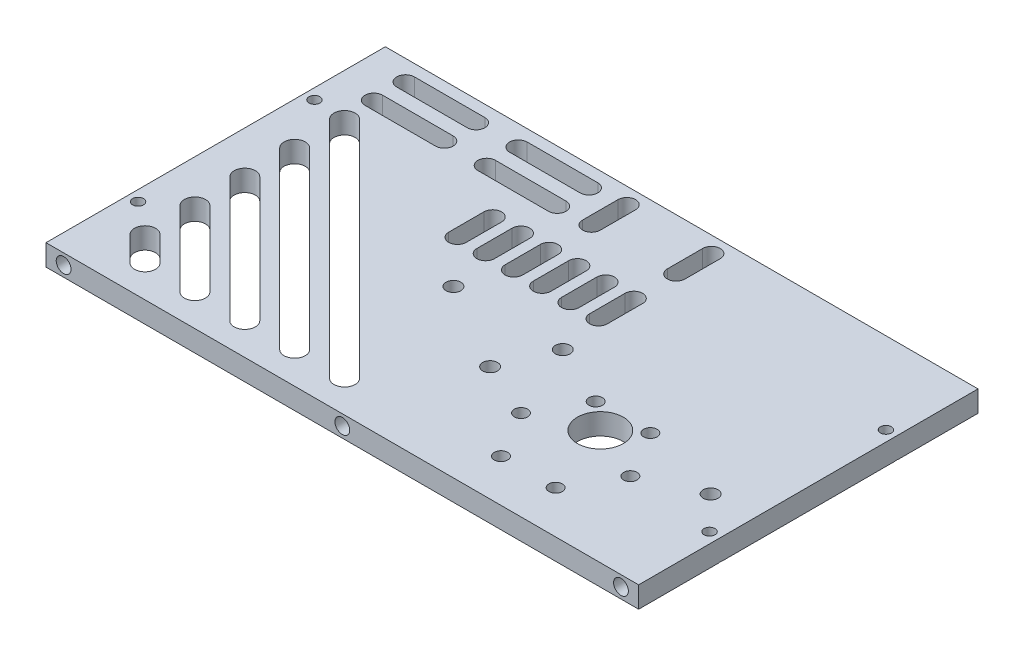
SolidWorks part; units mm, degrees
ref_plane "Front Plane" through (0, 0, 0) normal (1, 0, 0) x (0, 1, 0)
ref_plane "Top Plane" through (0, 0, 0) normal (0, 0, 1) x (0, 1, 0)
ref_plane "Right Plane" through (0, 0, 0) normal (0, 1, 0) x (-1, 0, 0)
sketch "Sketch1" plane through (0, 0, 0) normal (0, 1, 0) x (-1, 0, 0)
  line L3 (168, 0) -> (0, 0)
  line L10 (0, 96.2019) -> (168, 96.2019)
  line L15 (168, 96.2019) -> (168, 0)
  line L17 (0, 96.2019) -> (0, 0)
  point P16 (-5.5507, 58)
  point P19 (0, 0)
  point P27 (168, 0)
  dimension "D1" = 168
  dimension "D3" = 96.2019
extrude "Boss-Extrude1" add sketch "Sketch1" along normal blind 6 contours L10 L17 L3 L15 region at (-84, 0, 48.1009)
sketch "Sketch2" plane through (0, 0, 0) normal (0, -1, 0) x (1, 0, 0)
  line L0 (-93.9294, 6) -> (46.9505, 6) construction
  line L1 (-153.4835, 90.2019) -> (20.1803, 90.2019) construction
  line L2 (-28.5825, 49.2019) -> (48.7007, 49.2019) construction
  line L3 (-61.85, 63.025) -> (-61.85, 73.1366) construction
  line L4 (-168, 96.2019) -> (-168, 0) construction
  line L5 (-99.2651, 52.2019) -> (-68.3113, 52.2019) construction
  line L6 (-84, 47.6039) -> (-84, 23.5623) construction
  line L7 (-24.85, 55.8014) -> (-24.85, 50055.8014) construction
  line L8 (-10, 20.1758) -> (-10, 54.1601) construction
  line L9 (-156, 65.9887) -> (-134.7868, 87.2019) construction
  line L10 (-158.1213, 68.11) -> (-136.9081, 89.3232)
  line L11 (-153.8787, 63.8674) -> (-132.6655, 85.0806)
  line L12 (-156, 51.8466) -> (-120.6447, 87.2019) construction
  line L13 (-158.1213, 53.9679) -> (-122.766, 89.3232)
  line L14 (-153.8787, 49.7252) -> (-118.5233, 85.0806)
  line L15 (-156, 37.7044) -> (-106.5025, 87.2019) construction
  line L16 (-158.1213, 39.8257) -> (-108.6238, 89.3232)
  line L17 (-153.8787, 35.5831) -> (-104.3812, 85.0806)
  line L18 (-156, 23.5623) -> (-92.3604, 87.2019) construction
  line L19 (-158.1213, 25.6836) -> (-94.4817, 89.3232)
  line L20 (-153.8787, 21.441) -> (-90.2391, 85.0806)
  line L21 (-159, 102.2536) -> (-159, -2.1913) construction
  line L22 (0, 96.2019) -> (0, 0) construction
  line L23 (-43.35, 4.2203) -> (-43.35, -100.2246) construction
  line L24 (-156, 80.1308) -> (-148.9289, 87.2019) construction
  line L25 (-143.2721, 74.474) -> (-140.4437, 71.6456) construction
  line L26 (-136.201, 67.4029) -> (-133.3726, 64.5745) construction
  line L27 (-129.1299, 60.3318) -> (-126.3015, 57.5034) construction
  line L28 (-158.1213, 82.2522) -> (-151.0503, 89.3232)
  line L29 (-153.8787, 78.0095) -> (-146.8076, 85.0806)
  line L30 (-147.5147, 78.7166) -> (-150.3431, 81.545) construction
  line L31 (-168, 96.2019) -> (-168, 0) construction
  line L32 (-168, 0) -> (0, 0) construction
  line L33 (-43.35, 70.7019) -> (-43.35, 9.0934) construction
  line L35 (0, 96.2019) -> (-168, 96.2019) construction
  line L36 (0, 96.2019) -> (0, 0) construction
  circle A7 centre (-43.35, 63.7019) radius 6.5
  circle A9 centre (-43.35, 70.7019) radius 18.5 construction
  arc A11 (-158.1213, 68.11) -> (-153.8787, 63.8674) centre (-156, 65.9887) ccw
  arc A12 (-132.6655, 85.0806) -> (-136.9081, 89.3232) centre (-134.7868, 87.2019) ccw
  arc A13 (-158.1213, 53.9679) -> (-153.8787, 49.7252) centre (-156, 51.8466) ccw
  arc A14 (-118.5233, 85.0806) -> (-122.766, 89.3232) centre (-120.6447, 87.2019) ccw
  arc A15 (-158.1213, 39.8257) -> (-153.8787, 35.5831) centre (-156, 37.7044) ccw
  arc A16 (-104.3812, 85.0806) -> (-108.6238, 89.3232) centre (-106.5025, 87.2019) ccw
  arc A17 (-158.1213, 25.6836) -> (-153.8787, 21.441) centre (-156, 23.5623) ccw
  arc A18 (-90.2391, 85.0806) -> (-94.4817, 89.3232) centre (-92.3604, 87.2019) ccw
  arc A19 (-158.1213, 82.2522) -> (-153.8787, 78.0095) centre (-156, 80.1308) ccw
  arc A20 (-146.8076, 85.0806) -> (-151.0503, 89.3232) centre (-148.9289, 87.2019) ccw
  circle A21 centre (-43.35, 70.7019) radius 15.5 construction
  circle A22 centre (-58.85, 70.7019) radius 1.9
  circle A23 centre (-51.1, 84.1253) radius 1.9
  circle A24 centre (-35.6, 84.1253) radius 1.9
  circle A25 centre (-27.85, 70.7019) radius 1.9
  circle A26 centre (-35.6, 57.2785) radius 1.9
  circle A27 centre (-51.1, 57.2785) radius 1.9
  circle A32 centre (-43.35, 63.7019) radius 31.25 construction
  circle A33 centre (-74.6, 63.7019) radius 2.1
  circle A34 centre (-43.35, 94.9519) radius 2.1 construction
  circle A35 centre (-12.1, 63.7019) radius 2.1
  circle A36 centre (-43.35, 32.4519) radius 2.1 construction
  circle A37 centre (-68.5, 49.2019) radius 2.1
  circle A38 centre (-99.5, 49.2019) radius 2.1
  point P24 (-152.4645, 83.6664)
  point P45 (-145.3934, 76.5953)
  point P50 (-138.3223, 69.5242)
  point P57 (-131.2513, 62.4532)
  point P64 (-124.1802, 55.3821)
  dimension "D14" = 31
  dimension "D15" = 3.8
  dimension "D2" = 37
  dimension "D6" = 13
  dimension "D3" = 62.5
  dimension "D9" = 4.2
  dimension "D7" = 45
  dimension "D8" = 6
  dimension "D11" = 4
  dimension "D13" = 7
  dimension "D5" = 6
  dimension "D10" = 6
  dimension "D4" = 43.2019
  dimension "D17" = 10
  dimension "D19" = 10
  dimension "D20" = 9
  dimension "D12" = 31
  dimension "D21" = 3
  dimension "D16" = 6
  dimension "D18" = 4
extrude "Cut-Extrude1" cut sketch "Sketch2" against normal up to next
sketch "Sketch3" plane through (0, 0, 0) normal (0, 0, -1) x (1, 0, 0)
  line L2 (0, -3) -> (50000, -3) construction
  line L3 (0, -6) -> (0, 0) construction
  line L4 (-168, -6) -> (-168, 0) construction
  line L5 (-84, 0) -> (-84, -6) construction
  line L6 (-168, 0) -> (0, 0) construction
  line L7 (-168, -6) -> (0, -6) construction
  circle A0 centre (-5, -3) radius 2.1
  circle A1 centre (-163, -3) radius 2.1
  circle A2 centre (-84, -3) radius 2.1
  point P11 (0, -3)
  dimension "D1" = 4.2
  dimension "D3" = 5
  dimension "D2" = 5
extrude "Cut-Extrude2" cut sketch "Sketch3" against normal blind 15
extrude "Cut-Extrude3" cut sketch "Sketch3<3>" along normal blind 15 from surface starting at face at (-84, 3, 96.2019)
sketch "Sketch3<3>" plane through (0, 0, 0) normal (0, 0, -1) x (1, 0, 0) same geometry as "Sketch3"
sketch "Sketch4" plane through (0, 0, 0) normal (0, -1, 0) x (1, 0, 0)
  line L0 (-168, 48.1009) -> (0, 48.1009) construction
  line L1 (-165, 73.1009) -> (-3, 73.1009) construction
  line L2 (-165, 73.1009) -> (-165, 23.1009) construction
  line L3 (-165, 23.1009) -> (-3, 23.1009) construction
  line L4 (-3, 73.1009) -> (-3, 23.1009) construction
  line L5 (-168, 96.2019) -> (-168, 0) construction
  line L6 (0, 96.2019) -> (0, 0) construction
  circle A0 centre (-165, 73.1009) radius 1.55
  circle A1 centre (-165, 23.1009) radius 1.55
  circle A2 centre (-3, 23.1009) radius 1.55
  circle A3 centre (-3, 73.1009) radius 1.55
  dimension "D1" = 3.1
  dimension "D2" = 3
  dimension "D3" = 3
  dimension "D4" = 50
extrude "Cut-Extrude4" cut sketch "Sketch4" against normal up to next
sketch "Sketch5" plane through (0, 0, 0) normal (0, -1, 0) x (1, 0, 0)
  line L0 (-156.5, 14.7811) -> (-136.5, 14.7811) construction
  line L1 (-156.5, 17.2811) -> (-136.5, 17.2811)
  line L2 (-156.5, 12.2811) -> (-136.5, 12.2811)
  line L3 (-130.5, 20.5623) -> (-130.5, 0) construction
  line L6 (-168, 20.5623) -> (0, 20.5623) construction
  line L7 (-168, 96.2019) -> (-168, 0) construction
  line L8 (0, 96.2019) -> (0, 0) construction
  line L9 (-156.5, 5.7811) -> (-136.5, 5.7811) construction
  line L10 (-156.5, 8.2811) -> (-136.5, 8.2811)
  line L11 (-156.5, 3.2811) -> (-136.5, 3.2811)
  line L12 (-111, 36.5623) -> (-111, 26.5623) construction
  line L15 (-108.5, 36.5623) -> (-108.5, 26.5623)
  line L18 (-168, 10.2811) -> (0, 10.2811) construction
  line L19 (-159, 23.5623) -> (-159, 0) construction
  line L20 (-168, 0) -> (0, 0) construction
  line L21 (-104.5, 14.7811) -> (-124.5, 14.7811) construction
  line L22 (-104.5, 17.2811) -> (-124.5, 17.2811)
  line L23 (-104.5, 12.2811) -> (-124.5, 12.2811)
  line L24 (-113.5, 36.5623) -> (-113.5, 26.5623)
  line L27 (-104.5, 5.7811) -> (-124.5, 5.7811) construction
  line L28 (-104.5, 8.2811) -> (-124.5, 8.2811)
  line L29 (-104.5, 3.2811) -> (-124.5, 3.2811)
  line L30 (-103, 36.5623) -> (-103, 26.5623) construction
  line L33 (-100.5, 36.5623) -> (-100.5, 26.5623)
  line L34 (-105.5, 36.5623) -> (-105.5, 26.5623)
  line L35 (-95, 36.5623) -> (-95, 26.5623) construction
  line L36 (-92.5, 36.5623) -> (-92.5, 26.5623)
  line L37 (-97.5, 36.5623) -> (-97.5, 26.5623)
  line L38 (-87, 36.5623) -> (-87, 26.5623) construction
  line L39 (-84.5, 36.5623) -> (-84.5, 26.5623)
  line L40 (-89.5, 36.5623) -> (-89.5, 26.5623)
  line L41 (-79, 36.5623) -> (-79, 26.5623) construction
  line L42 (-76.5, 36.5623) -> (-76.5, 26.5623)
  line L43 (-81.5, 36.5623) -> (-81.5, 26.5623)
  line L44 (-71, 36.5623) -> (-71, 26.5623) construction
  line L45 (-68.5, 36.5623) -> (-68.5, 26.5623)
  line L46 (-73.5, 36.5623) -> (-73.5, 26.5623)
  line L51 (-113.5, 0) -> (-68.5, 0) construction
  line L52 (-113.5, 0) -> (-113.5, 39.0623) construction
  line L53 (-113.5, 39.0623) -> (-68.5, 39.0623) construction
  line L54 (-68.5, 0) -> (-68.5, 39.0623) construction
  line L69 (-71, 4.5623) -> (-71, 14.5623) construction
  line L70 (-68.5, 4.5623) -> (-68.5, 14.5623)
  line L71 (-73.5, 4.5623) -> (-73.5, 14.5623)
  line L72 (-79, 4.5623) -> (-79, 14.5623) construction
  line L73 (-76.5, 4.5623) -> (-76.5, 14.5623) construction
  line L74 (-81.5, 4.5623) -> (-81.5, 14.5623) construction
  line L75 (-87, 4.5623) -> (-87, 14.5623) construction
  line L76 (-84.5, 4.5623) -> (-84.5, 14.5623) construction
  line L77 (-89.5, 4.5623) -> (-89.5, 14.5623) construction
  line L78 (-95, 4.5623) -> (-95, 14.5623) construction
  line L79 (-92.5, 4.5623) -> (-92.5, 14.5623)
  line L80 (-97.5, 4.5623) -> (-97.5, 14.5623)
  line L81 (-103, 4.5623) -> (-103, 14.5623) construction
  line L82 (-100.5, 4.5623) -> (-100.5, 14.5623) construction
  line L83 (-105.5, 4.5623) -> (-105.5, 14.5623) construction
  line L84 (-111, 4.5623) -> (-111, 14.5623) construction
  line L85 (-108.5, 4.5623) -> (-108.5, 14.5623) construction
  line L86 (-113.5, 4.5623) -> (-113.5, 14.5623) construction
  arc A0 (-156.5, 17.2811) -> (-156.5, 12.2811) centre (-156.5, 14.7811) ccw
  arc A1 (-136.5, 12.2811) -> (-136.5, 17.2811) centre (-136.5, 14.7811) ccw
  arc A4 (-158.1213, 25.6836) -> (-153.8787, 21.441) centre (-156, 23.5623) ccw construction
  arc A5 (-156.5, 8.2811) -> (-156.5, 3.2811) centre (-156.5, 5.7811) ccw
  arc A6 (-136.5, 3.2811) -> (-136.5, 8.2811) centre (-136.5, 5.7811) ccw
  arc A11 (-104.5, 17.2811) -> (-104.5, 12.2811) centre (-104.5, 14.7811) cw
  arc A12 (-124.5, 12.2811) -> (-124.5, 17.2811) centre (-124.5, 14.7811) cw
  arc A15 (-104.5, 8.2811) -> (-104.5, 3.2811) centre (-104.5, 5.7811) cw
  arc A16 (-124.5, 3.2811) -> (-124.5, 8.2811) centre (-124.5, 5.7811) cw
  arc A19 (-108.5, 36.5623) -> (-113.5, 36.5623) centre (-111, 36.5623) ccw
  arc A20 (-113.5, 26.5623) -> (-108.5, 26.5623) centre (-111, 26.5623) ccw
  arc A21 (-100.5, 36.5623) -> (-105.5, 36.5623) centre (-103, 36.5623) ccw
  arc A22 (-105.5, 26.5623) -> (-100.5, 26.5623) centre (-103, 26.5623) ccw
  arc A23 (-92.5, 36.5623) -> (-97.5, 36.5623) centre (-95, 36.5623) ccw
  arc A24 (-97.5, 26.5623) -> (-92.5, 26.5623) centre (-95, 26.5623) ccw
  arc A25 (-84.5, 36.5623) -> (-89.5, 36.5623) centre (-87, 36.5623) ccw
  arc A26 (-89.5, 26.5623) -> (-84.5, 26.5623) centre (-87, 26.5623) ccw
  arc A27 (-76.5, 36.5623) -> (-81.5, 36.5623) centre (-79, 36.5623) ccw
  arc A28 (-81.5, 26.5623) -> (-76.5, 26.5623) centre (-79, 26.5623) ccw
  arc A29 (-68.5, 36.5623) -> (-73.5, 36.5623) centre (-71, 36.5623) ccw
  arc A30 (-73.5, 26.5623) -> (-68.5, 26.5623) centre (-71, 26.5623) ccw
  arc A44 (-68.5, 4.5623) -> (-73.5, 4.5623) centre (-71, 4.5623) cw
  arc A45 (-73.5, 14.5623) -> (-68.5, 14.5623) centre (-71, 14.5623) cw
  arc A46 (-76.5, 4.5623) -> (-81.5, 4.5623) centre (-79, 4.5623) cw construction
  arc A47 (-81.5, 14.5623) -> (-76.5, 14.5623) centre (-79, 14.5623) cw construction
  arc A48 (-84.5, 4.5623) -> (-89.5, 4.5623) centre (-87, 4.5623) cw construction
  arc A49 (-89.5, 14.5623) -> (-84.5, 14.5623) centre (-87, 14.5623) cw construction
  arc A50 (-92.5, 4.5623) -> (-97.5, 4.5623) centre (-95, 4.5623) cw
  arc A51 (-97.5, 14.5623) -> (-92.5, 14.5623) centre (-95, 14.5623) cw
  arc A52 (-100.5, 4.5623) -> (-105.5, 4.5623) centre (-103, 4.5623) cw construction
  arc A53 (-105.5, 14.5623) -> (-100.5, 14.5623) centre (-103, 14.5623) cw construction
  arc A54 (-108.5, 4.5623) -> (-113.5, 4.5623) centre (-111, 4.5623) cw construction
  arc A55 (-113.5, 14.5623) -> (-108.5, 14.5623) centre (-111, 14.5623) cw construction
  point P2 (-146.5, 14.7811)
  point P11 (-114.5, 14.7811)
  point P26 (-146.5, 5.7811)
  point P31 (-111, 31.5623)
  point P40 (-103, 31.5623)
  point P55 (-95, 31.5623)
  point P62 (-114.5, 5.7811)
  point P69 (-87, 31.5623)
  point P76 (-79, 31.5623)
  point P83 (-71, 31.5623)
  point P138 (-71, 9.5623)
  point P145 (-79, 9.5623)
  point P152 (-87, 9.5623)
  point P159 (-95, 9.5623)
  point P166 (-103, 9.5623)
  point P173 (-111, 9.5623)
  dimension "D1" = 2
  dimension "D2" = 5
  dimension "D3" = 4
  dimension "D4" = 20
  dimension "D5" = 6
  dimension "D6" = 5
  dimension "D7" = 10
  dimension "D8" = 6
  dimension "D10" = 3
  dimension "D9" = 6
extrude "Cut-Extrude5" cut sketch "Sketch5" against normal up to next
chamfer "Chamfer1" distance 1.5 distance2 2 4 edges at (-3, 0, 71.551) (-3, 0, 21.5509) (-165, 0, 21.5509) (-165, 0, 71.551) first distance on face at (-79, 0, 31.5623)
equation "\"MotorDriverLength\"= 60mm"
equation "\"MotorLength\"= 60"
equation "\"MotorDriverWidth\"=44"
equation "\"MotorWidth\"= 37"
equation "\"InnerWallThickness\"=3"
equation "\"BatteryWidth\"= 60"
equation "\"OuterWallThickness\" = 6"
equation "\"CompartmentHeight\"=37"
equation "\"CompartmentWidth\"= \"MotorDriverLength\""
equation "\"MotorDiameter\"=37"
equation "\"BatteryHeight\"=24.2019"
equation "\"MotorDriverHeight\"=28"
equation "\"CircuitHeight\"=30"
equation "\"FanThickness\"= 10"
equation "\"FanHeight\"=50"
equation "\"D1@Boss-Extrude1\" = \"OuterWallThickness\""
equation "\"MotorShaftHole\"=12"
equation "\"BearingBore\"=4"
equation "\"MinShinWidth\"= 20"
equation "\"ShinThickness\"=10"
equation "\"PivotDistance\"=30"
equation "\"ThighLength\"= 200"
equation "\"HipBore\"=27"
equation "\"ThighThickness\"=20"
equation "\"MaxBending\"=135"
equation "\"MaxStretchingAngle\"= 140"
equation "\"ThighJointDistance\"=157.485"
equation "\"ShinLength\"=120"
equation "\"BearingDiameter\"= 10"
equation "\"D2@Sketch2\"=\"MotorDiameter\""
equation "\"D6@Sketch2\"=\"MotorShaftHole\"+1"
equation "\"D5@Sketch2\"=\"OuterWallThickness\""
equation "\"D10@Sketch2\"=\"OuterWallThickness\""
equation "\"D4@Sketch2\"=\"BatteryHeight\"+\"OuterWallThickness\"*1.5+10"
equation "\"GearboxDiameter\"= 62.5"
equation "\"D1@Sketch1\" = \"ChessisInnerWidth\""
equation "\"ChessisInnerWidth\"= \"OuterWallThickness\" * 2 + \"MotorDriverLength\" + \"MotorDiameter\" + \"InnerWallThickness\" * 3 + \"CircuitLength\""
equation "\"CircuitLength\"=50"
equation "\"D3@Sketch1\" = \"ChessisHeight\""
equation "\"D3@Sketch2\"=\"GearboxDiameter\""
equation "\"D17@Sketch2\"=\"OuterWallThickness\"+4"
equation "\"D20@Sketch2\"=\"OuterWallThickness\"+3"
equation "\"ChessisHeight\"= \"BatteryHeight\" + 10 + \"InnerWallThickness\" + \"MotorDiameter\" + 10 + \"OuterWallThickness\" * 2"
equation "\"D3@Sketch4\"=\"OuterWallThickness\"/2"
equation "\"D2@Sketch4\"=\"OuterWallThickness\"/2"
